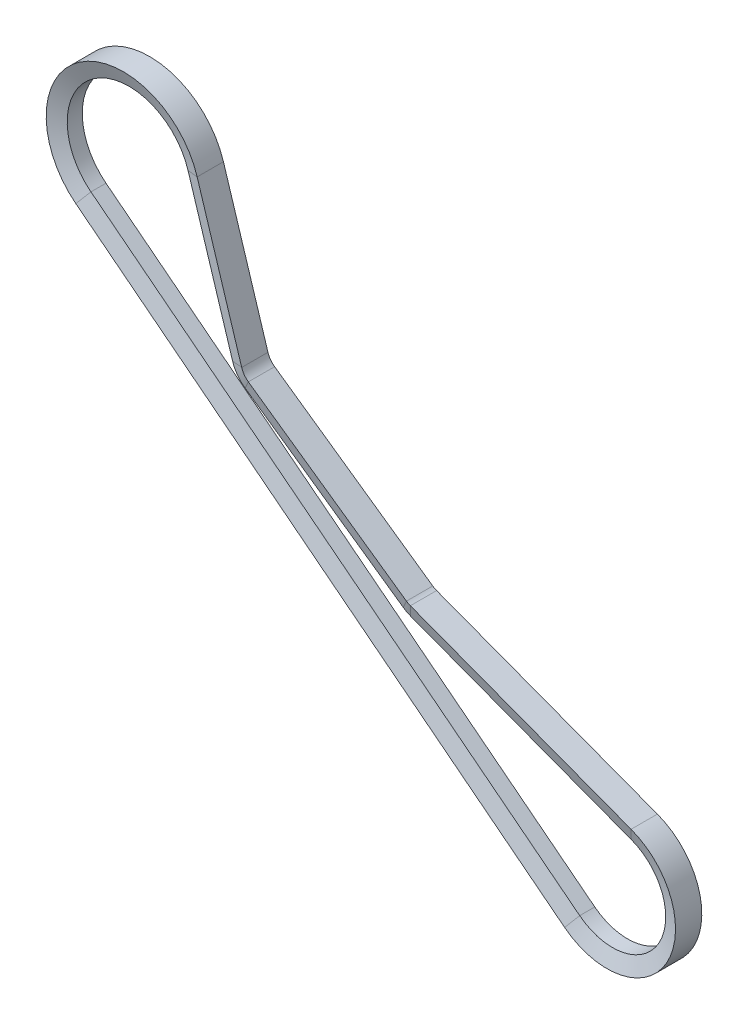
SolidWorks part; units mm, degrees
ref_plane "Front Plane" through (0, 0, 0) normal (0, 0, 1) x (1, 0, 0)
ref_plane "Top Plane" through (0, 0, 0) normal (0, 1, 0) x (1, 0, 0)
ref_plane "Right Plane" through (0, 0, 0) normal (1, 0, 0) x (0, 0, -1)
sketch "Sketch2" plane through (0, 0, 0) normal (0, 0, 1) x (1, 0, 0)
  line L0 (0, 0) -> (1, 0) construction
  line L1 (0, 0) -> (0, 1) construction
  line L12 (-15.3282, -19.5911) -> (-192.5174, 119.0423)
  line L14 (-148.5329, 149.4297) -> (-132.3943, 97.6734)
  line L15 (-129.9775, 94.3643) -> (-72.661, 54.1794)
  line L16 (-71.2551, 53.4368) -> (8.7724, 23.2768)
  arc A4 (-192.5174, 119.0423) -> (-148.5329, 149.4297) centre (-175.2636, 141.0946) cw
  arc A7 (8.7724, 23.2768) -> (-15.3282, -19.5911) centre (0, 0) cw
  arc A8 (-132.3943, 97.6734) -> (-129.9775, 94.3643) centre (-126.3322, 99.5637) ccw
  arc A9 (-72.661, 54.1794) -> (-71.2551, 53.4368) centre (-69.0157, 59.3788) ccw
ref_plane "Plane4" through (8.7724, 23.2768, 0) normal (0.9358, -0.3527, 0) x (-0.3527, -0.9358, 0)
sketch "Sketch3" plane through (8.7724, 23.2768, 0) normal (0.9358, -0.3527, 0) x (-0.3527, -0.9358, 0)
  line L0 (0, -4.7625) -> (0, 4.7625)
  line L1 (0, -4.7625) -> (5.588, -2.7286)
  line L2 (5.588, -2.7286) -> (5.588, 2.7286)
  line L3 (5.588, 2.7286) -> (0, 4.7625)
  line L4 (0, 0) -> (5.588, 0) construction
  dimension "D1" = 9.525
  dimension "D2" = 5.588
  dimension "D3" = 40
sweep "Sweep1" add profiles "Sketch3" path "Sketch2"
